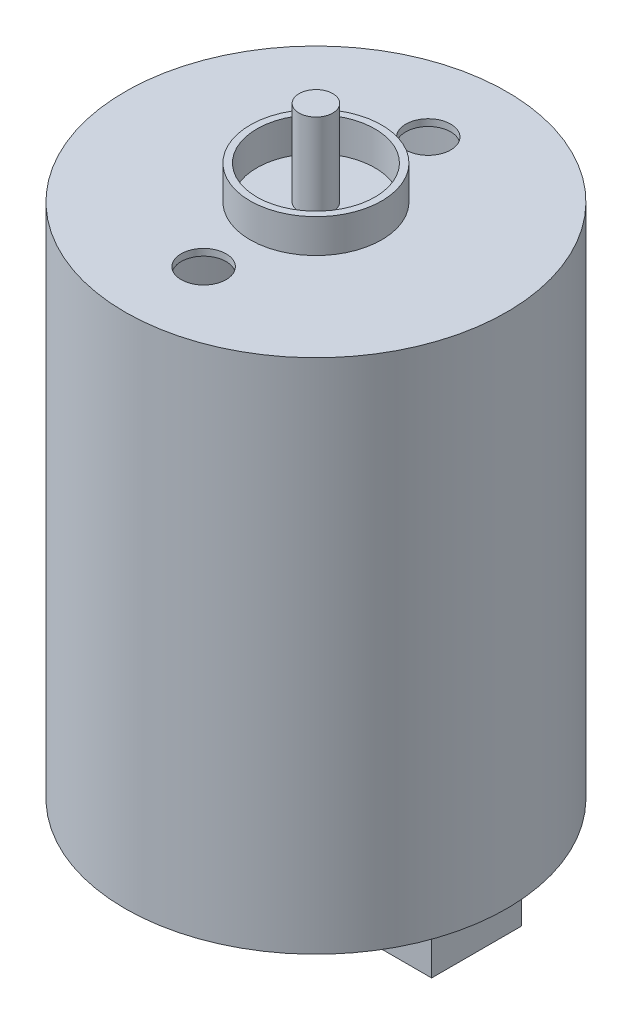
SolidWorks part; units mm, degrees
ref_plane "Front Plane" through (0, 0, 0) normal (0, 0, 1) x (1, 0, 0)
ref_plane "Top Plane" through (0, 0, 0) normal (0, 1, 0) x (1, 0, 0)
ref_plane "Right Plane" through (0, 0, 0) normal (1, 0, 0) x (0, 0, -1)
sketch "Sketch1" plane through (0, 0, 0) normal (0, 1, 0) x (1, 0, 0)
  circle A0 centre (0, 0) radius 8.5
extrude "Boss-Extrude1" add sketch "Sketch1" along normal blind 23
shell "Shell3" thickness 0.3 removed face at (0, 0, 8.5)
ref_plane "Plane2" through (0, 0.5, 0) normal (0, -1, 0) x (-1, 0, 0)
sketch "Sketch2" plane through (0, 0.5, 0) normal (0, -1, 0) x (-1, 0, 0)
  circle A0 centre (0, 0) radius 8.2
extrude "Boss-Extrude2" add sketch "Sketch2" against normal blind 0.3
sketch "Sketch3" plane through (0, 0.5, 0) normal (0, -1, 0) x (1, 0, 0)
  circle A0 centre (0, 0) radius 1.15
extrude "Boss-Extrude3" add sketch "Sketch3" along normal blind 1.5
sketch "Sketch4" plane through (0, 23, 0) normal (0, 1, 0) x (1, 0, 0)
  circle A0 centre (0, 0) radius 2.9296
  circle A1 centre (0, 0) radius 2.6296
  dimension "D1" = 0.3
extrude "Boss-Extrude4" add sketch "Sketch4" along normal blind 1.5
sketch "Sketch5" plane through (0, 23, 0) normal (0, 1, 0) x (1, 0, 0)
  circle A0 centre (0, 0) radius 0.75
  dimension "D1" = 1.5
extrude "Boss-Extrude5" add sketch "Sketch5" along normal blind 3.8
ref_plane "Plane3" through (0, 26.825, 0) normal (0, 1, 0) x (1, 0, 0)
sketch "Sketch7" plane through (0, 23, 0) normal (0, 1, 0) x (1, 0, 0)
  circle A0 centre (0, 5) radius 1
  circle A1 centre (0, -5) radius 1
  dimension "D3" = 2
  dimension "D4" = 2
  dimension "D1" = 5
  dimension "D2" = 5
extrude "Cut-Extrude1" cut sketch "Sketch7" against normal up to next
sketch "Sketch8" plane through (0, 0.5, 0) normal (0, -1, 0) x (1, 0, 0)
  line L1 (-7.15, 2) -> (-4.85, 2)
  line L2 (-7.15, 2) -> (-7.15, -2)
  line L3 (-7.15, -2) -> (-4.85, -2)
  line L4 (-4.85, 2) -> (-4.85, -2)
  line L5 (-7.15, 2) -> (-4.85, -2) construction
  line L6 (-7.15, -2) -> (-4.85, 2) construction
  line L7 (4.85, 2) -> (7.15, 2)
  line L8 (4.85, 2) -> (4.85, -2)
  line L9 (4.85, -2) -> (7.15, -2)
  line L10 (7.15, 2) -> (7.15, -2)
  line L11 (4.85, 2) -> (7.15, -2) construction
  line L12 (4.85, -2) -> (7.15, 2) construction
  point P0 (-6, 0)
  point P5 (6, 0)
  dimension "D1" = 4
  dimension "D2" = 2.3
  dimension "D3" = 4
  dimension "D4" = 2.3
  dimension "D5" = 6
  dimension "D6" = 6
  dimension "D7" = 0
  dimension "D8" = 0
extrude "Boss-Extrude7" add sketch "Sketch8" along normal blind 2.85
